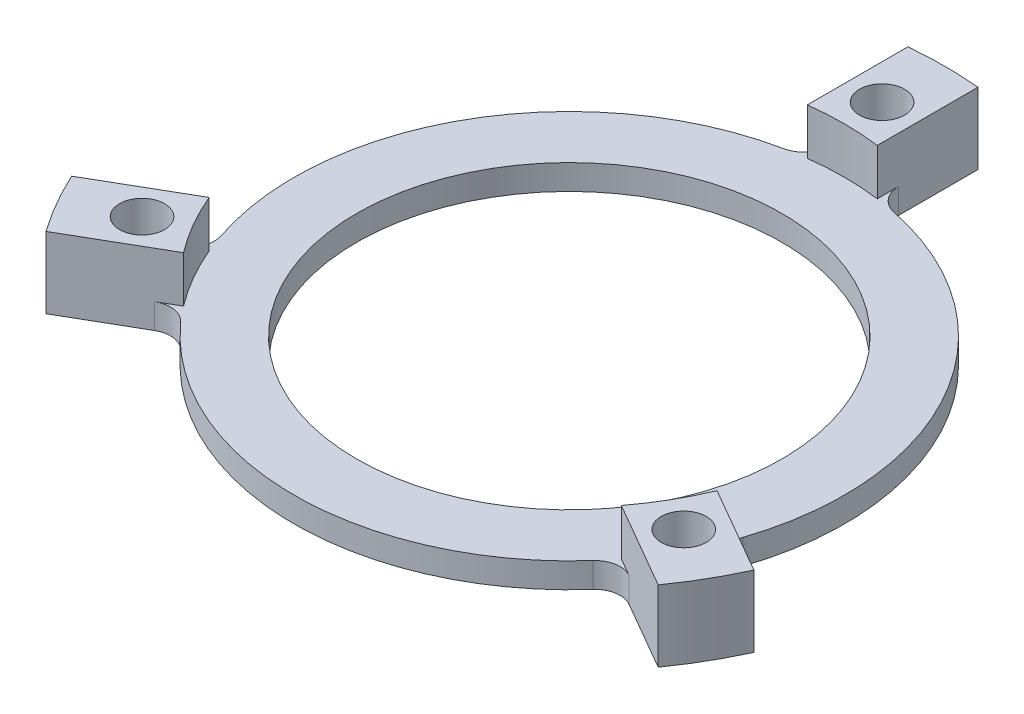
SolidWorks part; units mm, degrees
material "Delrin 2700 NC010, Low Viscosity Acetal Copolymer (SS)"
ref_plane "Front" through (0, 0, 0) normal (0, 0, 1) x (1, 0, 0)
ref_plane "Top" through (0, 0, 0) normal (0, 1, 0) x (1, 0, 0)
ref_plane "Right" through (0, 0, 0) normal (1, 0, 0) x (0, 0, -1)
sketch "Sketch1" plane through (0, 0, 0) normal (0, 1, 0) x (1, 0, 0)
  line L0 (0, 11) -> (0, 15) construction
  line L1 (-1.4, 15) -> (1.4, 15)
  line L2 (-1.4, 15) -> (-1.4, 10.9105)
  line L3 (1.4, 15) -> (1.4, 10.9105)
  line L4 (12.2904, -8.7124) -> (8.7488, -6.6677)
  line L5 (13.6904, -6.2876) -> (10.1488, -4.2428)
  line L6 (13.6904, -6.2876) -> (12.2904, -8.7124)
  line L7 (-13.6904, -6.2876) -> (-10.1488, -4.2428)
  line L8 (-12.2904, -8.7124) -> (-8.7488, -6.6677)
  line L9 (-12.2904, -8.7124) -> (-13.6904, -6.2876)
  circle A0 centre (0, 0) radius 11
  circle A1 centre (0, 0) radius 15
  circle A2 centre (0, 12.5) radius 0.9
  circle A5 centre (0, 0) radius 8.5
  circle A6 centre (10.8253, -6.25) radius 0.9
  circle A7 centre (-10.8253, -6.25) radius 0.9
  point P12 (0, 15)
  dimension "D1" = 22
  dimension "D2" = 1.8
  dimension "D3" = 30
  dimension "D5" = 17
  dimension "D4" = 2.8
  dimension "D7" = 12.5
  dimension "D6" = 3
extrude "Boss-Extrude1" add sketch "Sketch1" along normal blind 2.85 contours L7 A1 L8 A0 A7 | A0 L0 A2 A1 L2 | L0 A0 L3 A1 A2 | L4 A1 L5 A0 A6 region at (-0.7942, 0, -13.1132) region at (0.7942, 0, -13.1132) region at (-9.5834, 0, 5.533) region at (11.8582, 0, 5.306)
extrude "Boss-Extrude2" add sketch "Sketch1<3>" along normal blind 1 contours A0 A5 region at (0, 0, -10.6889)
sketch "Sketch1<3>" plane through (0, 0, 0) normal (0, 1, 0) x (1, 0, 0) same geometry as "Sketch1"
fillet "Fillet1" radius 1 6 edges at (1.4, 0.5, -10.9105) (10.1488, 0.5, 4.2428) (8.7488, 0.5, 6.6677) (-1.4, 0.5, -10.9105) (-10.1488, 0.5, 4.2428) (-8.7488, 0.5, 6.6677)
